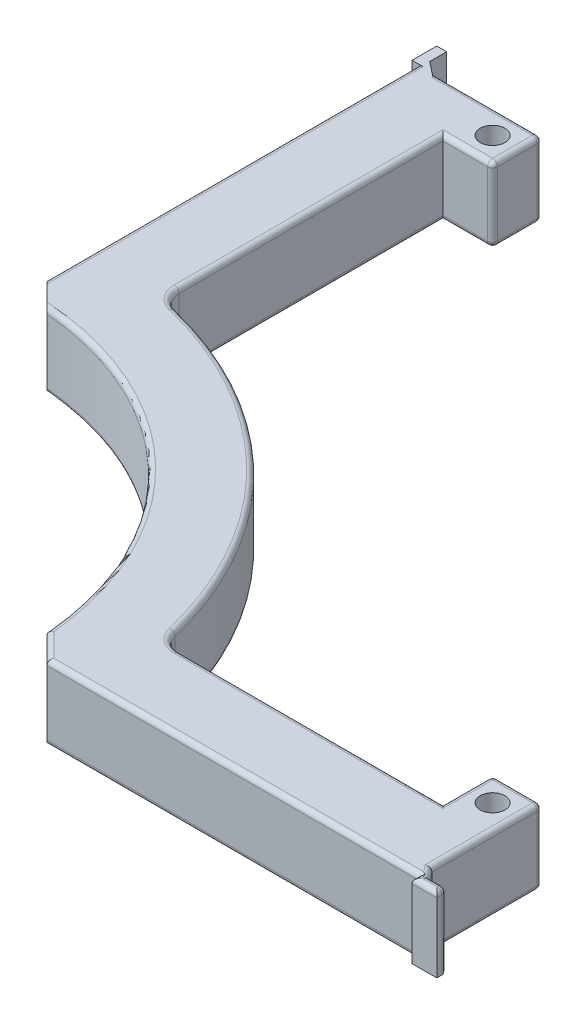
SolidWorks part; units mm, degrees
ref_plane "Front Plane" through (0, 0, 0) normal (0, 0, 1) x (1, 0, 0)
ref_plane "Top Plane" through (0, 0, 0) normal (0, 1, 0) x (1, 0, 0)
ref_plane "Right Plane" through (0, 0, 0) normal (1, 0, 0) x (0, 0, -1)
sketch "Sketch1" plane through (0, 0, 0) normal (0, 1, 0) x (1, 0, 0)
  line L0 (0, 0) -> (0, -6.35)
  line L1 (0, -6.35) -> (1.6002, -6.35)
  line L2 (1.6002, -6.35) -> (1.6002, -107.95)
  line L3 (1.6002, -186.309) -> (169.3349, -18.5743) construction
  line L4 (0, 0) -> (2.54, 0)
  line L5 (2.54, 0) -> (2.54, -4.3818)
  line L6 (2.54, -4.3818) -> (5.08, -6.35)
  line L7 (5.08, -6.35) -> (33.3502, -6.35)
  line L8 (33.3502, -6.35) -> (33.3502, -19.05)
  line L9 (33.3502, -19.05) -> (20.6502, -19.05)
  line L10 (20.6502, -19.05) -> (20.6502, -90.7809)
  line L12 (168.8592, -167.259) -> (97.1283, -167.259)
  line L13 (168.8592, -154.559) -> (168.8592, -167.259)
  line L14 (181.5592, -154.559) -> (168.8592, -154.559)
  line L15 (181.5592, -182.8292) -> (181.5592, -154.559)
  line L16 (183.5274, -185.3692) -> (181.5592, -182.8292)
  line L17 (187.9092, -185.3692) -> (183.5274, -185.3692)
  line L18 (187.9092, -187.9092) -> (187.9092, -185.3692)
  line L19 (187.9092, -187.9092) -> (181.5592, -187.9092)
  line L20 (181.5592, -187.9092) -> (181.5592, -186.309)
  line L21 (181.5592, -186.309) -> (79.9592, -186.309)
  arc A0 (1.6002, -107.95) -> (79.9592, -186.309) centre (1.6002, -186.309) cw
  arc A1 (20.6502, -90.7809) -> (97.1283, -167.259) centre (1.6002, -186.309) cw
  circle A2 centre (27.0002, -12.7) radius 3.175
  circle A3 centre (175.2092, -160.909) radius 3.175
  dimension "D4" = 78.359
  dimension "D5" = 0
  dimension "D7" = 97.409
  dimension "D15" = 6.35
  dimension "D1" = 0
  dimension "D2" = 45
  dimension "D6" = 19.05
  dimension "D8" = 1.6002
  dimension "D9" = 6.35
  dimension "D10" = 2.54
  dimension "D11" = 0
  dimension "D12" = 2.54
  dimension "D13" = 12.7
  dimension "D14" = 12.7
  dimension "D16" = 6.35
  dimension "D17" = 6.35
  dimension "D18" = 101.6
extrude "Boss-Extrude1" add sketch "Sketch1" along normal blind 19.05
chamfer "Chamfer1" distance 6.35 angle 45 2 edges at (79.9592, 9.525, 186.309) (1.6002, 9.525, 107.95)
fillet "Fillet1" radius 5.08 2 edges at (97.1283, 9.525, 167.259) (20.6502, 9.525, 90.7809)
fillet "Fillet2" radius 1.27 40 edges at (135.0337, 0, 167.259) (98.0672, 0, 166.1716) (20.6502, 0, 52.8755) (21.7376, 0, 89.842) (135.0337, 19.05, 167.259) (98.0672, 19.05, 166.1716) (20.6502, 19.05, 52.8755) (21.7376, 19.05, 89.842) (187.9092, 9.525, 185.3692) (185.7183, 0, 185.3692) (182.5433, 0, 184.0992) (168.8592, 0, 160.909) (175.2092, 0, 154.559) (181.5592, 0, 168.6941) (168.8592, 9.525, 154.559) (181.5592, 9.525, 154.559) (33.3502, 0, 12.7) (33.3502, 9.525, 19.05) (33.3502, 19.05, 12.7) (33.3502, 9.525, 6.35) (19.2151, 0, 6.35) (19.2151, 19.05, 6.35) (27.0002, 19.05, 19.05) (27.0002, 0, 19.05) (1.6002, 19.05, 53.975) (1.6002, 0, 53.975) (57.0084, 0, 130.9008) (181.5592, 19.05, 187.1091) (184.7342, 19.05, 187.9092) (187.9092, 19.05, 186.6392) (182.5433, 19.05, 184.0992) (185.7183, 19.05, 185.3692) (181.5592, 19.05, 168.6941) (175.2092, 19.05, 154.559) (168.8592, 19.05, 160.909) (82.9937, 19.05, 182.9935) (133.9342, 19.05, 186.309) (57.0084, 19.05, 130.9008) (70.4788, 0, 117.4304) (70.4788, 19.05, 117.4304)
fillet "Fillet3" radius 1.27 1 edges at (133.9342, 0, 186.309)
